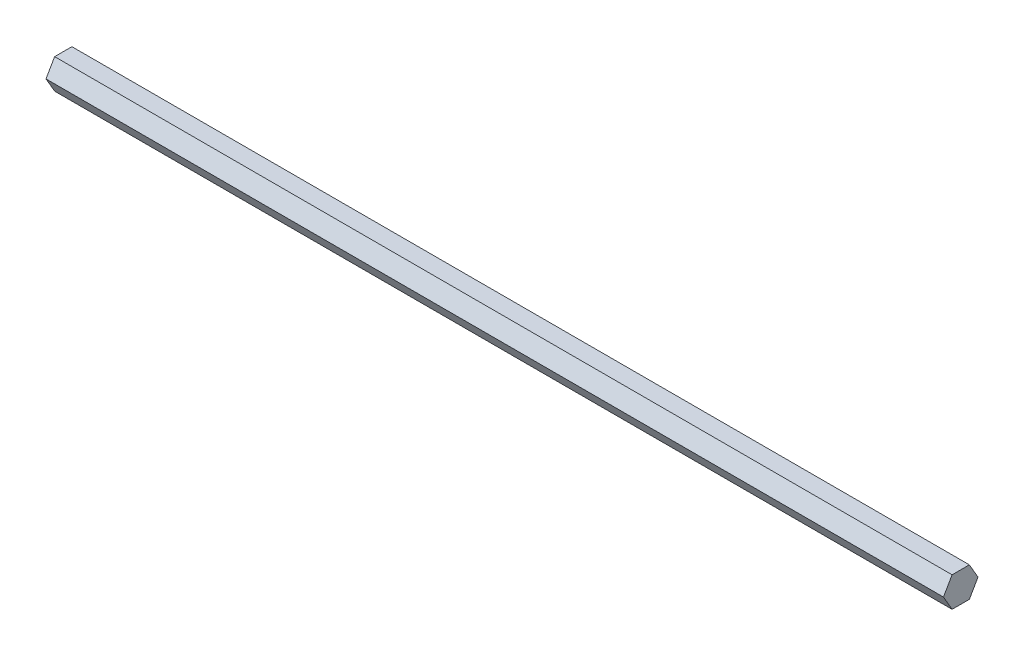
SolidWorks part; units mm, degrees
material "7075-T6 (SN)"
ref_plane "Front Plane" through (0, 0, 0) normal (0, 0, 1) x (1, 0, 0)
ref_plane "Top Plane" through (0, 0, 0) normal (0, 1, 0) x (1, 0, 0)
ref_plane "Right Plane" through (0, 0, 0) normal (1, 0, 0) x (0, 0, -1)
sketch "Sketch1" plane through (0, 0, 0) normal (1, 0, 0) x (0, 0, -1)
  line L1 (7.3323, 0) -> (3.6662, 6.35)
  line L2 (3.6662, 6.35) -> (-3.6662, 6.35)
  line L3 (-3.6662, 6.35) -> (-7.3323, 0)
  line L4 (-7.3323, 0) -> (-3.6662, -6.35)
  line L5 (-3.6662, -6.35) -> (3.6662, -6.35)
  line L6 (3.6662, -6.35) -> (7.3323, 0)
  circle A0 centre (0, 0) radius 6.35 construction
  dimension "D1" = 12.7
extrude "Boss-Extrude1" add sketch "Sketch1" along normal mid plane 381
ref_axis "Axis1" through (-230.505, 0, 0) along (1, 0, 0)
